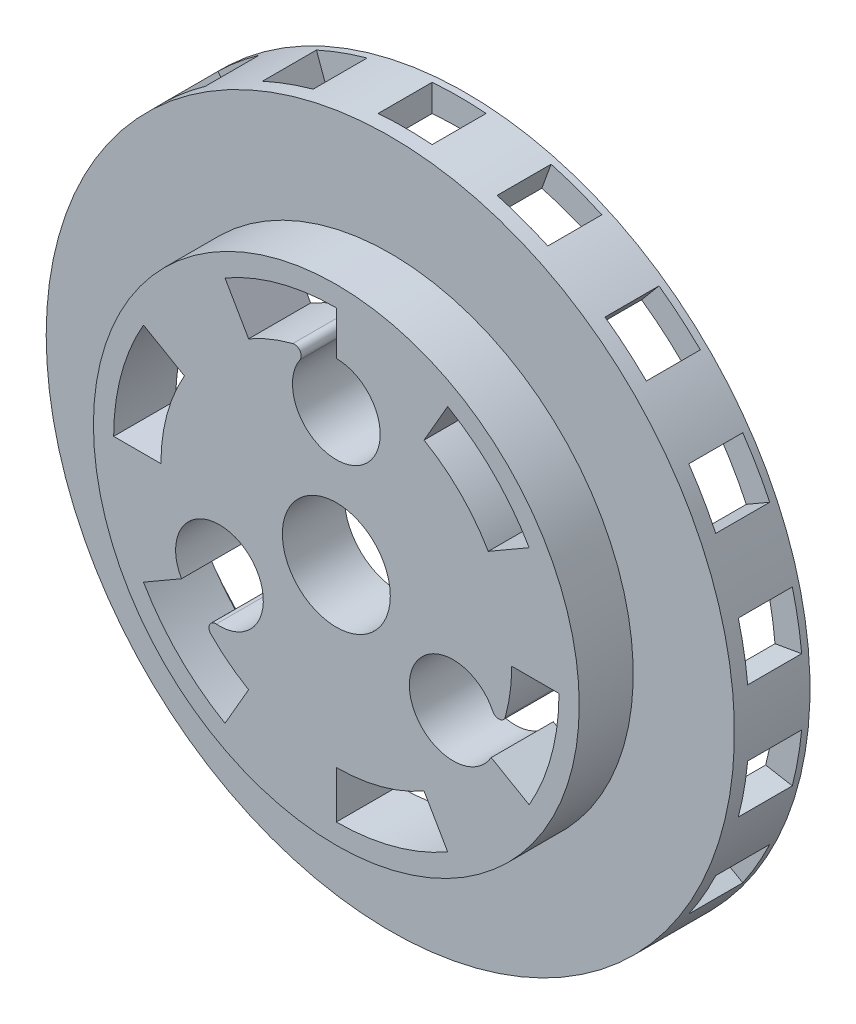
SolidWorks part; units mm, degrees
ref_plane "Plan de face" through (0, 0, 0) normal (0, 0, 1) x (1, 0, 0)
ref_plane "Plan de dessus" through (0, 0, 0) normal (0, 1, 0) x (1, 0, 0)
ref_plane "Plan de droite" through (0, 0, 0) normal (1, 0, 0) x (0, 0, -1)
sketch "Esquisse1" plane through (0, 0, 0) normal (0, 0, 1) x (1, 0, 0)
  circle A0 centre (0, 0) radius 18
  dimension "D1" = 36
extrude "Boss.-Extru.1" add sketch "Esquisse1" along normal blind 4
sketch "Esquisse5" plane through (0, 0, 0) normal (0, 0, -1) x (-1, 0, 0)
  circle A0 centre (0, 0) radius 25.5
  dimension "D1" = 51
extrude "Boss.-Extru.2" add sketch "Esquisse5" along normal blind 0.6
sketch "Esquisse2" plane through (0, 0, 4) normal (0, 0, 1) x (1, 0, 0)
  line L0 (0, 13) -> (0, 16.5)
  line L1 (-8.25, 14.2894) -> (-6.5, 11.2583)
  arc A0 (0, 16.5) -> (-8.25, 14.2894) centre (0, 0) ccw
  arc A1 (0, 13) -> (-6.5, 11.2583) centre (0, 0) ccw
  dimension "D1" = 33
  dimension "D2" = 26
  dimension "D3" = 30
extrude "Enlèv. mat.-Extru.1" cut sketch "Esquisse2" against normal through all
sketch "Esquisse4" plane through (0, 0, 4) normal (0, 0, 1) x (1, 0, 0)
  circle A0 centre (0, 0) radius 4
  dimension "D1" = 8
extrude "Enlèv. mat.-Extru.3" cut sketch "Esquisse4" against normal through all
pattern_circular "Répétition circulaire1" count 6 over 360 about axis through (0, 0, 4) along (0, 0, 1) of "Enlèv. mat.-Extru.1"
sketch "Esquisse3" plane through (0, 0, 4) normal (0, 0, 1) x (1, 0, 0)
  circle A0 centre (0, 10) radius 3.25
  dimension "D2" = 6.5
  dimension "D1" = 10
extrude "Enlèv. mat.-Extru.2" cut sketch "Esquisse3" against normal through all
pattern_circular "Répétition circulaire2" count 3 over 360 about axis through (0, 0, 4) along (0, 0, 1) of "Enlèv. mat.-Extru.2"
fillet "Congé1" radius 0.5 3 edges at (11.9022, -5.2285, 1.7) (-10.4791, -7.6934, 1.7) (-1.4231, 12.9219, 1.7)
sketch "Esquisse6" plane through (0, 0, -0.6) normal (0, 0, -1) x (-1, 0, 0)
  circle A0 centre (0, 0) radius 25.5
  circle A1 centre (0, 0) radius 23.5
  circle A2 centre (0, 0) radius 25.5 construction
  dimension "D1" = 2
extrude "Boss.-Extru.3" add sketch "Esquisse6" along normal blind 5
ref_plane "Plan1" through (0, 25.5, 0) normal (0, 1, 0) x (1, 0, 0)
sketch "Esquisse7" plane through (0, 25.5, 0) normal (0, 1, 0) x (1, 0, 0)
  line L2 (0, -2.2) -> (0, 2.2) construction
  line L3 (2, 1.1) -> (-2, 1.1)
  line L4 (2, 1.1) -> (2, 5.1)
  line L5 (2, 5.1) -> (-2, 5.1)
  line L6 (-2, 1.1) -> (-2, 5.1)
  line L7 (2, 1.1) -> (-2, 5.1) construction
  line L8 (2, 5.1) -> (-2, 1.1) construction
  line L9 (25.5, 5.6) -> (-25.5, 5.6) construction
  point P0 (0, 3.1)
  dimension "D2" = 4
  dimension "D1" = 4
  dimension "D3" = 0
  dimension "D4" = 2.5
extrude "Enlèv. mat.-Extru.4" cut sketch "Esquisse7" against normal blind 4
ref_axis "Axe1" through (0, 0, -0.6) along (0, 0, 1)
pattern_circular "Répétition circulaire3" count 18 every 20 about axis through (0, 0, -0.6) along (0, 0, 1) of "Enlèv. mat.-Extru.4"
